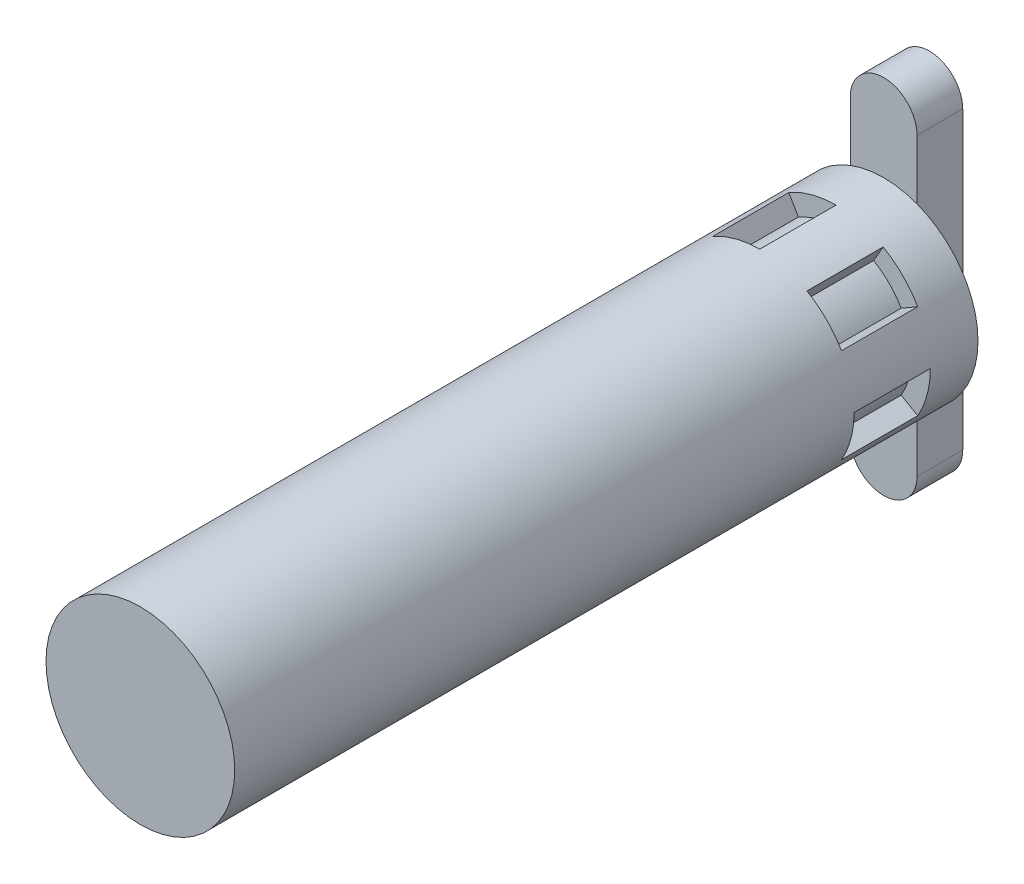
SolidWorks part; units mm, degrees
material "ABS"
ref_plane "前视基准面" through (0, 0, 0) normal (0, 0, 1) x (1, 0, 0)
ref_plane "上视基准面" through (0, 0, 0) normal (0, 1, 0) x (1, 0, 0)
ref_plane "右视基准面" through (0, 0, 0) normal (1, 0, 0) x (0, 0, -1)
sketch "草图1" plane through (0, 0, 0) normal (0, 0, 1) x (1, 0, 0)
  circle A0 centre (0, 0) radius 4.95
  dimension "D1" = 9.9
extrude "凸台-拉伸1" add sketch "草图1" along normal blind 4.5
sketch "草图2" plane through (0, 0, 0) normal (0, 0, -1) x (-1, 0, 0)
  line L0 (0, 4.95) -> (0, 3.95)
  line L1 (1.975, 3.4208) -> (2.475, 4.2868)
  arc A0 (0, 4.95) -> (2.475, 4.2868) centre (0, 0) cw
  circle A1 centre (0, 0) radius 4.95 construction
  arc A2 (0, 3.95) -> (1.975, 3.4208) centre (0, 0) cw
  dimension "D1" = 30
  dimension "D2" = 1
extrude "切除-拉伸1" cut sketch "草图2" against normal blind 2
pattern_circular "阵列(圆周)1" count 6 over 360 about axis through (0, 0, 4.5) along (0, 0, 1) of "切除-拉伸1"
mirror "镜向1" about plane through (0, 0, 0) normal (0, 0, 1) of "凸台-拉伸1", "切除-拉伸1", "阵列(圆周)1"
sketch "草图3" plane through (0, 0, -4.5) normal (0, 0, -1) x (-1, 0, 0)
  line L0 (0, 7.75) -> (0, -7.75) construction
  line L1 (1.75, 7.75) -> (1.75, -7.75)
  line L2 (-1.75, 7.75) -> (-1.75, -7.75)
  arc A0 (1.75, 7.75) -> (-1.75, 7.75) centre (0, 7.75) ccw
  arc A1 (-1.75, -7.75) -> (1.75, -7.75) centre (0, -7.75) ccw
  point P3 (0, 0)
  point P8 (0, 0)
  point P9 (0, 9.5)
  point P10 (0, -9.5)
  dimension "D1" = 19
  dimension "D2" = 3.5
extrude "凸台-拉伸2" add sketch "草图3" along normal blind 2.4
sketch "草图5" plane through (0, 0, 4.5) normal (0, 0, 1) x (1, 0, 0)
  circle A1 centre (0, 0) radius 4.95
  circle A2 centre (0, 0) radius 4.95
  dimension "D1" = 0
extrude "凸台-拉伸3" add sketch "草图5" along normal blind 30
